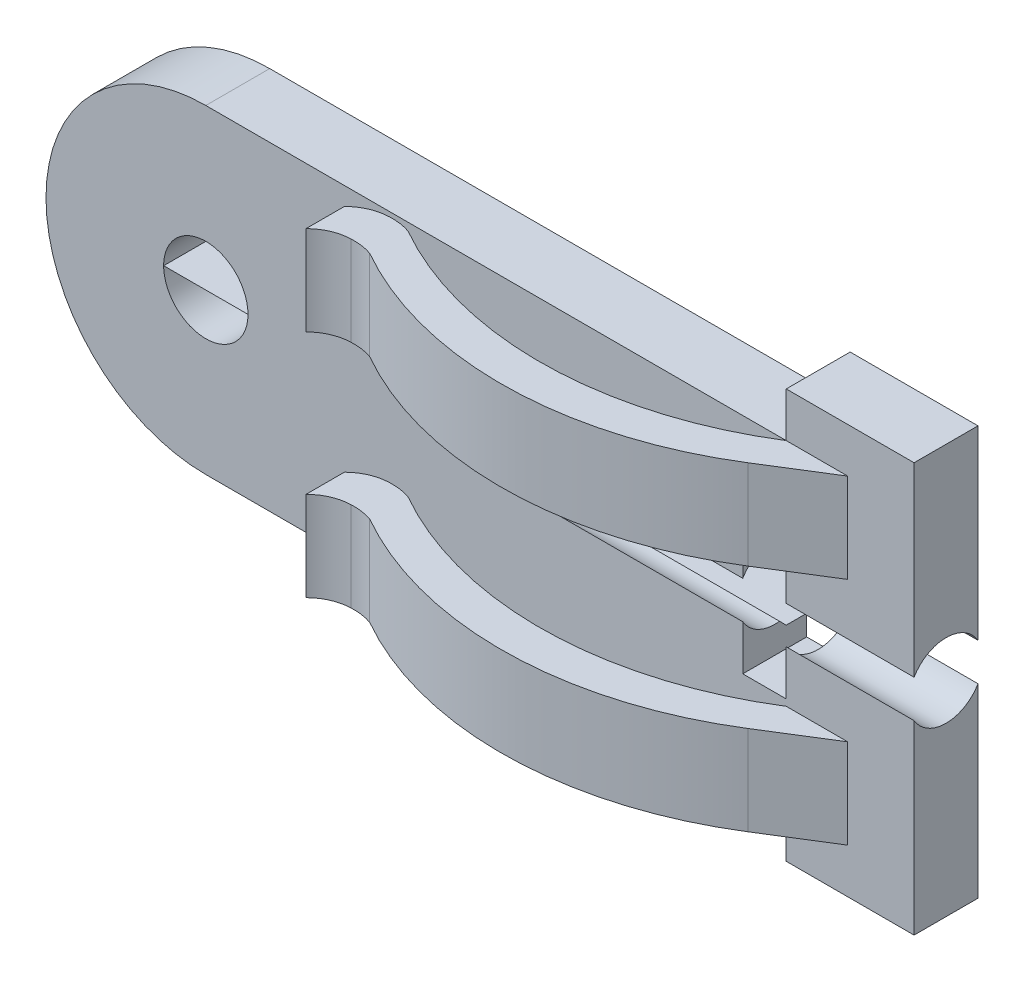
SolidWorks part; units mm, degrees
ref_plane "Front Plane" through (0, 0, 0) normal (0, 0, 1) x (1, 0, 0)
ref_plane "Top Plane" through (0, 0, 0) normal (0, 1, 0) x (1, 0, 0)
ref_plane "Right Plane" through (0, 0, 0) normal (1, 0, 0) x (0, 0, -1)
sketch "Sketch1" plane through (0, 0, 0) normal (0, 0, 1) x (1, 0, 0)
  line L0 (0, -6.25) -> (22.7, -6.25)
  line L1 (-12.7, 12.7) -> (12.7, 12.7)
  line L2 (-12.7, 12.7) -> (-12.7, -12.7)
  line L3 (-12.7, -12.7) -> (12.7, -12.7)
  line L4 (12.7, 12.7) -> (12.7, -12.7)
  line L5 (0, 6.25) -> (22.7, 6.25)
  line L6 (22.7, 6.25) -> (22.7, -6.25)
  circle A0 centre (0, 0) radius 1.65
  arc A1 (0, 6.25) -> (0, -6.25) centre (0, 0) ccw
  dimension "D1" = 3.3
  dimension "D3" = 25.4
  dimension "D4" = 25.4
  dimension "D5" = 12.7
  dimension "D6" = 12.7
  dimension "D7" = 10
extrude "Boss-Extrude1" add sketch "Sketch1" along normal blind 2.5 contours L5 A1 L0 L4 A0 | L6 L5 L4 L0 region at (3.9956, 0, 0) region at (17.7, 0, 0)
sketch "Sketch2" plane through (0, 0, 2.5) normal (0, 0, 1) x (1, 0, 0)
  line L1 (22.7, -8) -> (27.7, -8)
  line L2 (22.7, -8) -> (22.7, 8)
  line L3 (22.7, 8) -> (27.7, 8)
  line L4 (27.7, -8) -> (27.7, 8)
  circle A0 centre (0, 0) radius 1.65 construction
  dimension "D1" = 5
  dimension "D2" = 16
  dimension "D3" = 8
extrude "Boss-Extrude2" add sketch "Sketch2" against normal blind 2.5
sketch "Sketch3" plane through (0, 0, 2.5) normal (0, 0, 1) x (1, 0, 0)
  line L0 (22.7, 8) -> (22.7, 6.25) construction
  line L1 (22.7, 2.5) -> (21, 2.5)
  line L2 (22.7, 2.5) -> (22.7, -2.5)
  line L3 (22.7, -2.5) -> (21, -2.5)
  line L4 (21, 2.5) -> (21, -2.5)
  circle A0 centre (0, 0) radius 1.65 construction
  dimension "D1" = 1.7
  dimension "D2" = 0
  dimension "D3" = 5
  dimension "D4" = 2.5
extrude "Cut-Extrude1" cut sketch "Sketch3" against normal through all
sketch "Sketch6" plane through (27.7, 0, 0) normal (1, 0, 0) x (0, 0, -1)
  line L0 (-2.5, -8) -> (-2.5, 8) construction
  line L1 (0, -8) -> (-2.5, -8) construction
  line L2 (0, 8) -> (-2.5, 8) construction
  circle A0 centre (-1.25, 0) radius 1.45
  point P6 (-1.25, 8)
  dimension "D4" = 2.9
  dimension "D1" = 1.25
  dimension "D2" = 8
  dimension "D3" = 8
extrude "Cut-Extrude3" cut sketch "Sketch6" against normal blind 16.7
sketch "Sketch7" plane through (0, -6.25, 0) normal (0, -1, 0) x (1, 0, 0)
  line L1 (6.1299, 3.2107) -> (6.1299, 4.7107)
  line L3 (22.7, 4) -> (22.7, 2.5)
  arc A0 (22.7, 2.5) -> (8.2067, 2.7997) centre (15.2027, -9.4701) ccw
  arc A1 (7.3606, 2.6809) -> (6.1299, 3.2107) centre (7.409, 4.4878) cw
  arc A2 (7.3606, 2.6809) -> (8.2067, 2.7997) centre (7.4758, 4.9321) ccw
  arc A3 (7.3606, 4.1809) -> (6.1299, 4.7107) centre (7.409, 5.9878) cw
  arc A4 (22.7, 4) -> (8.2067, 4.2997) centre (15.2027, -7.9701) ccw
  arc A5 (7.3606, 4.1809) -> (8.2067, 4.2997) centre (7.4758, 6.4321) ccw
  dimension "D3" = 2
  dimension "D1" = 1.5
extrude "Boss-Extrude3" add sketch "Sketch7" against normal blind 3.5 separate body
surface "Surface-MidSurface1" parameters "D0"=50000
sketch "Sketch9" plane through (0, -6.25, 0) normal (0, -1, 0) x (1, 0, 0)
  line L0 (22.7, 4) -> (25.1049, 2.5)
  line L1 (25.1049, 2.5) -> (22.7, 2.5)
  line L2 (22.7, 2.5) -> (22.7, 4)
extrude "Boss-Extrude5" add sketch "Sketch9" against normal blind 3.5 separate body
combine bodies "Combine1" operation type add bodies to combine 111 106
mirror "Mirror4" about plane through (0, 0, 2.5) normal (0, 1, 0) of bodies 112
